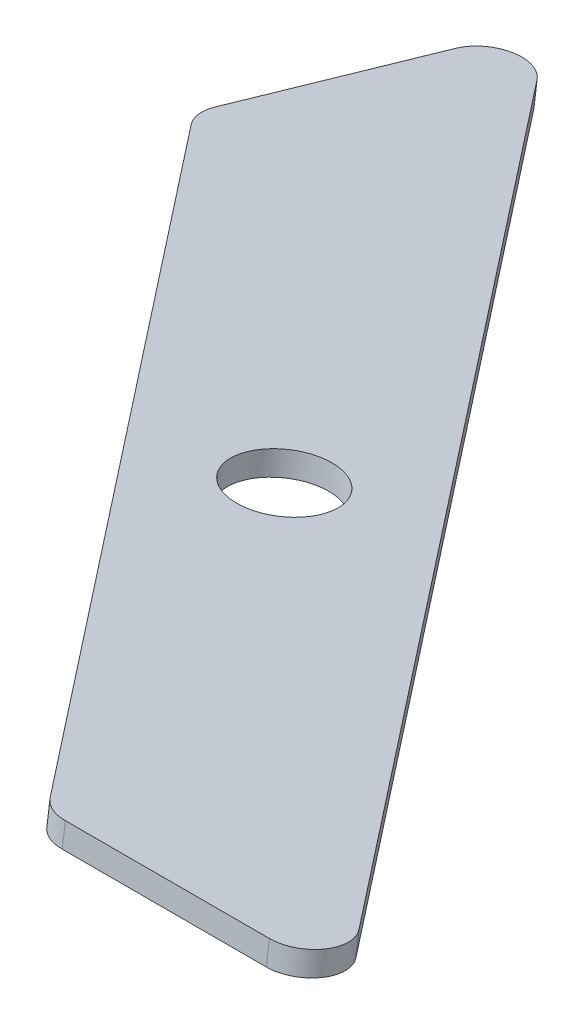
SolidWorks part; units mm, degrees
material "Plain Carbon Steel"
ref_plane "Front Plane" through (0, 0, 0) normal (0, 0, 1) x (1, 0, 0)
ref_plane "Top Plane" through (0, 0, 0) normal (0, 1, 0) x (1, 0, 0)
ref_plane "Right Plane" through (0, 0, 0) normal (1, 0, 0) x (0, 0, -1)
ref_axis "Axis1" through (319.3358, -763.9745, 172.6811) along (-0.2127, 0.1285, 0.9686)
ref_axis "Axis2" through (-326.2058, -768.1262, 141.3977) along (0.2127, 0.1285, 0.9686)
ref_axis "Axis3" through (201.261, -691.9258, 717.5541) along (-1, 0, 0)
ref_plane "Plane1" through (0, -773.2722, 102.6213) normal (0, 0.9913, -0.1316) x (1, 0, 0)
ref_plane "Plane2" through (0, -785.8618, 104.2921) normal (0, -0.9913, 0.1316) x (-1, 0, 0)
sketch "Sketch1" plane through (0, -785.8618, 104.2921) normal (0, -0.9913, 0.1316) x (-1, 0, 0)
  line L0 (-211.3417, -566.75) -> (-254.4801, -620.2899)
  line L1 (-319.3358, -70.674) -> (-203.2004, -604.1475) construction
  line L2 (-201.261, -620.2899) -> (201.2079, -620.2899) construction
  line L3 (-254.4801, -620.2899) -> (-274.8669, -620.2899)
  line L4 (-274.8669, -620.2899) -> (-215.6783, -546.8297)
  line L5 (-215.6783, -546.8297) -> (-211.3417, -566.75)
  line L6 (-213.51, -556.7899) -> (-264.6735, -620.2899) construction
  line L7 (-215.6783, -546.8297) -> (-254.4801, -620.2899) construction
  line L8 (-274.8669, -620.2899) -> (-211.3417, -566.75) construction
  circle A0 centre (-239.0917, -588.5399) radius 3.2639
  dimension "D2" = 6.5278
  dimension "D3" = 31.75
  dimension "D1" = 15.875
extrude "Boss-Extrude1" add sketch "Sketch1" along normal blind 1.5875
fillet "Fillet1" radius 2.54 4 edges at (274.8669, -705.0452, 719.2952) (254.4801, -705.0452, 719.2952) (211.3417, -712.0887, 666.2207) (215.6783, -714.7094, 646.4735)
